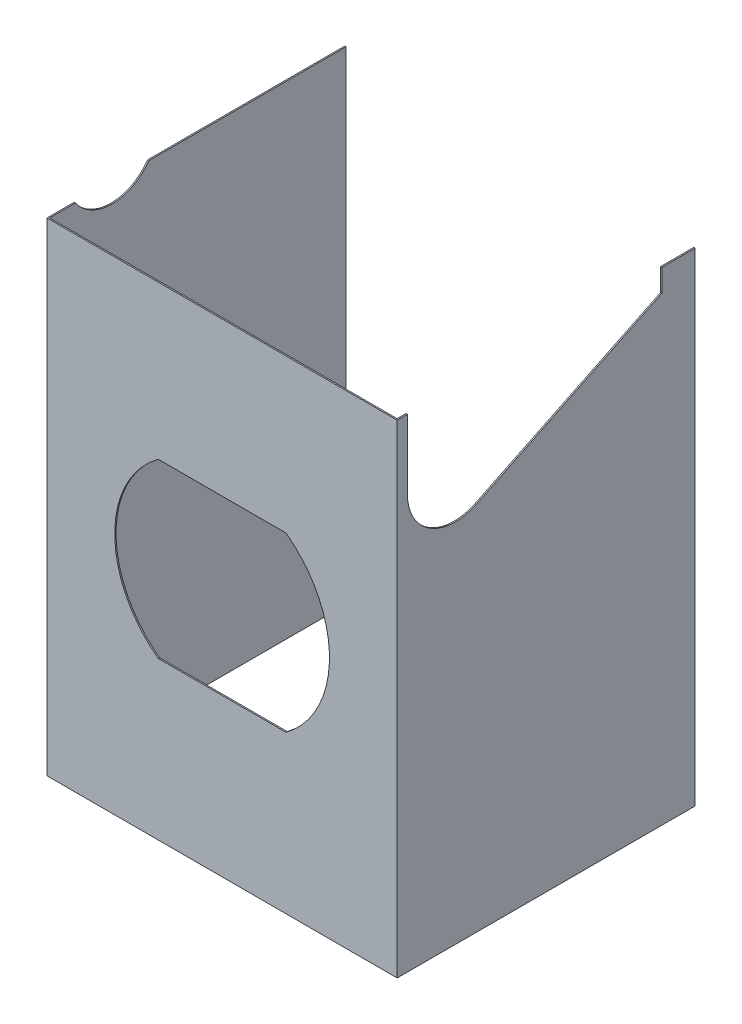
SolidWorks part; units mm, degrees
material "Nickel"
ref_plane "Front Plane" through (0, 0, 0) normal (0, 0, 1) x (1, 0, 0)
ref_plane "Top Plane" through (0, 0, 0) normal (0, 1, 0) x (1, 0, 0)
ref_plane "Right Plane" through (0, 0, 0) normal (1, 0, 0) x (0, 0, -1)
sketch "Sketch1" plane through (0, 0, 0) normal (0, 0, 1) x (1, 0, 0)
  line L0 (-12.6994, -16.764) -> (12.6994, -16.764)
  line L1 (-34.798, -48.006) -> (34.798, -48.006)
  line L2 (-34.798, -48.006) -> (-34.798, 48.006)
  line L3 (-34.798, 48.006) -> (34.798, 48.006)
  line L4 (34.798, -48.006) -> (34.798, 48.006)
  line L5 (-34.798, -48.006) -> (34.798, 48.006) construction
  line L6 (-34.798, 48.006) -> (34.798, -48.006) construction
  line L7 (-12.704, 17.526) -> (12.704, 17.526)
  line L8 (0, 17.526) -> (0, -16.764) construction
  arc A0 (-12.6994, 17.526) -> (-12.3403, -17.0242) centre (0, 0.381) ccw
  arc A1 (12.3403, -17.0242) -> (12.6994, 17.526) centre (0, 0.381) ccw
  point P0 (0, 0)
  dimension "D5" = 42.672
  dimension "D1" = 96.012
  dimension "D2" = 69.596
  dimension "D3" = 31.242
  dimension "D4" = 30.48
extrude "Boss-Extrude1" add sketch "Sketch1" against normal blind 0.254 contours L1 L4 L3 L2 A1 L0 A0 L7 region at (-33.6122, 0, 0)
sketch "Sketch3" plane through (0, 0, 0) normal (0, 0, 1) x (1, 0, 0)
  line L0 (-34.798, -48.006) -> (-34.798, 48.006) construction
  line L1 (-34.798, -17.018) -> (34.798, -17.018)
  line L2 (-34.798, -17.018) -> (-34.798, -17.526)
  line L3 (-34.798, -17.526) -> (34.798, -17.526)
  line L4 (34.798, -17.018) -> (34.798, -17.526)
  line L5 (34.798, -48.006) -> (34.798, 48.006) construction
  line L6 (-12.6994, -16.764) -> (12.6994, -16.764) construction
  dimension "D1" = 0.508
  dimension "D2" = 0.254
extrude "Boss-Extrude2" add sketch "Sketch3" along normal blind 0.254 contours L2 L1 L4 L3
sketch "Sketch6" plane through (0, 0, 0) normal (0, 0, 1) x (1, 0, 0)
  line L0 (-34.798, -48.006) -> (34.798, -48.006) construction
  line L1 (14.986, -48.006) -> (15.24, -48.006)
  line L2 (-14.986, -48.006) -> (-15.24, -48.006)
  arc A0 (15.24, -48.006) -> (-15.24, -48.006) centre (0, -48.006) ccw
  arc A1 (14.986, -48.006) -> (-14.986, -48.006) centre (0, -48.006) ccw
  dimension "D1" = 30.48
  dimension "D2" = 29.972
extrude "Boss-Extrude6" add sketch "Sketch6" along normal blind 0.254
fillet "Fillet6" radius 0.254 2 edges at (0, -33.02, 0.254) (0, -32.766, 0.254)
ref_plane "Plane1" through (34.798, 0, 0) normal (1, 0, 0) x (0, 0, -1)
sketch "Sketch8" plane through (34.798, 0, 0) normal (1, 0, 0) x (0, 0, -1)
  line L1 (0, -48.006) -> (59.182, -48.006)
  line L2 (0, -48.006) -> (0, 48.0096)
  line L3 (0, 48.0096) -> (59.182, 48.0096)
  line L4 (59.182, -48.006) -> (59.182, 48.0096)
  dimension "D1" = 59.182
extrude "Boss-Extrude8" add sketch "Sketch8" against normal blind 0.254
sketch "Sketch9" plane through (34.798, 0, 0) normal (1, 0, 0) x (0, 0, -1)
  line L0 (2.032, 34.2259) -> (2.032, 48.0096)
  line L3 (15.7138, 25.6558) -> (52.578, 43.5364)
  line L4 (0, -17.018) -> (0, 48.0096) construction
  line L5 (2.032, 48.0096) -> (52.578, 48.0096)
  line L6 (59.182, 48.0096) -> (0, 48.0096) construction
  line L7 (52.578, 48.0096) -> (52.578, 43.5364)
  arc A0 (2.032, 34.2259) -> (15.7138, 25.6558) centre (11.557, 34.2259) ccw
  dimension "D1" = 19.05
  dimension "D3" = 2.032
  dimension "D4" = 6.604
extrude "Cut-Extrude1" cut sketch "Sketch9" against normal blind 0.254
ref_plane "Plane2" through (-34.798, 0, 0) normal (1, 0, 0) x (0, 0, -1)
sketch "Sketch12" plane through (-34.798, 0, 0) normal (1, 0, 0) x (0, 0, -1)
  line L1 (0, 48.006) -> (59.182, 48.006)
  line L2 (0, 48.006) -> (0, -48.006)
  line L3 (0, -48.006) -> (59.182, -48.006)
  line L4 (59.182, 48.006) -> (59.182, -48.006)
extrude "Boss-Extrude10" add sketch "Sketch12" along normal blind 0.254
sketch "Sketch13" plane through (-34.798, 0, 0) normal (-1, 0, 0) x (0, 0, 1)
  circle A0 centre (-12.7, 53.086) radius 8.89
  dimension "D1" = 17.78
extrude "Cut-Extrude3" cut sketch "Sketch13" against normal blind 0.254
ref_plane "Plane3" through (-32.258, 0, 0) normal (1, 0, 0) x (0, 0, -1)
ref_plane "Plane4" through (0, 0, 0) normal (1, 0, 0) x (0, 0, -1)
ref_plane "Plane5" through (15.113, -48.006, 0.22) normal (0, 1, 0) x (1, 0, 0)
sketch "Sketch24" plane through (34.798, 0, 0) normal (1, 0, 0) x (0, 0, -1)
  line L1 (0, -48.006) -> (-13.8363, -48.006)
  line L2 (0, -48.006) -> (0, -4.1214)
  line L3 (0, -4.1214) -> (-13.8363, -4.1214)
  line L4 (-13.8363, -48.006) -> (-13.8363, -4.1214)
extrude "Cut-Extrude5" cut sketch "Sketch24" against normal through all
